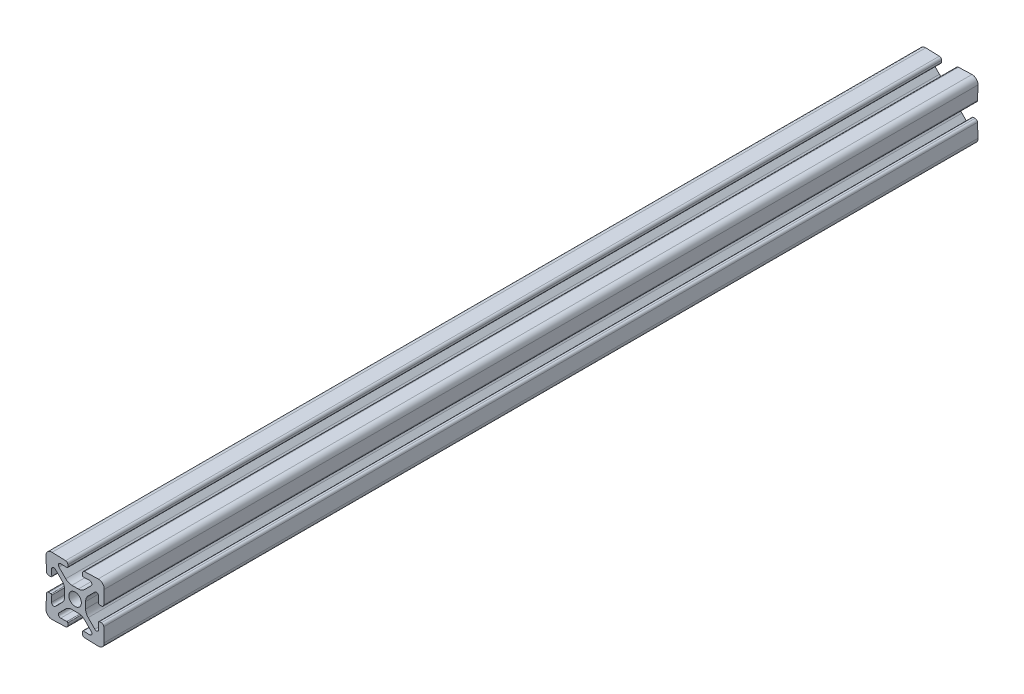
SolidWorks part; units mm, degrees
ref_plane "Front Plane" through (0, 0, 0) normal (0, 0, 1) x (1, 0, 0)
ref_plane "Top Plane" through (0, 0, 0) normal (0, 1, 0) x (1, 0, 0)
ref_plane "Right Plane" through (0, 0, 0) normal (1, 0, 0) x (0, 0, -1)
sketch "Sketch1" plane through (0, 0, 0) normal (0, 0, 1) x (1, 0, 0)
  line L0 (0, 0) -> (0, 10) construction
  line L1 (0, 0) -> (10, 0) construction
  line L2 (0, 0) -> (-10, 10) construction
  line L3 (-7.9302, 9.9988) -> (-3.2721, 9.8361)
  line L4 (-10, 10) -> (0, 10) construction
  line L6 (-2.8352, 8.0198) -> (-4.953, 8.0937)
  line L10 (0, 3.6) -> (-1.1022, 3.6)
  line L11 (-3.2236, 4.4787) -> (-5.5244, 6.7796)
  line L24 (0, 0) -> (-10, 0) construction
  line L25 (-10, 0) -> (0, 0) construction
  line L26 (0, 0) -> (0, -10) construction
  line L27 (-10, -10) -> (-10, 10) construction
  line L28 (0, 10) -> (10, 10) construction
  line L29 (-2.5249, 8.3091) -> (-2.5005, 9.0087)
  line L30 (-10, -10) -> (10, -10) construction
  arc A0 (-9.4142, 9.4142) -> (-7.9302, 9.9988) centre (-8, 8) cw
  arc A5 (-3.2721, 9.8361) -> (-2.5005, 9.0087) centre (-3.3, 9.0366) cw
  arc A6 (-1.1022, 3.6) -> (-3.2236, 4.4787) centre (-1.1022, 6.6) cw
  circle A16 centre (0, 0) radius 2.15
  arc A18 (-5.5244, 6.7796) -> (-4.953, 8.0937) centre (-4.9799, 7.3241) cw
  arc A20 (-2.8352, 8.0198) -> (-2.5249, 8.3091) centre (-2.8247, 8.3196) ccw
  point P15 (0, 0)
  point P42 (-2.3449, 3.6)
  point P80 (-10, 0)
  point P85 (0, -10)
  point P88 (0, -10)
  dimension "D11" = 2
  dimension "D15" = 3
  dimension "D4" = 0.7701
  dimension "D3" = 1.775
  dimension "Center Hole Diameter" = 4.3
  dimension "D5" = 11.5
  dimension "D6" = 9.9598
  dimension "D7" = 0.8
  dimension "D8" = 0.3
  dimension "D1" = 45
  dimension "D2" = 2
  dimension "Rail Width" = 20
  dimension "T-Slot Width" = 5
  dimension "D9" = 1.8
  dimension "D23" = 7.2
  dimension "T-Slot Depth" = 6.4
  dimension "Rail Height" = 20
sketch "Sketch3" plane through (0, 0, 0) normal (0, 0, 1) x (1, 0, 0)
  line L0 (-2.5249, 8.3091) -> (-2.5005, 9.0087) construction
  line L1 (0, 0) -> (-10, 10) construction
  line L2 (0, 0) -> (-10, 10) construction
  line L5 (-7.9302, 9.9988) -> (-3.2721, 9.8361) construction
  line L6 (-2.8352, 8.0198) -> (-4.953, 8.0937) construction
  line L17 (-2.5249, 8.3091) -> (-2.5005, 9.0087)
  line L19 (-2.8352, 8.0198) -> (-4.953, 8.0937)
  line L20 (0, 0) -> (0, 10) construction
  line L21 (-3.6, 0) -> (-2.15, 0)
  line L22 (-3.6, 0) -> (-3.6, 1.1022)
  line L23 (-4.4787, 3.2236) -> (-6.7796, 5.5244)
  line L42 (-3.2236, 4.4787) -> (-5.5244, 6.7796) construction
  line L43 (0, 3.6) -> (-1.1022, 3.6) construction
  line L44 (-7.9302, 9.9988) -> (-3.2721, 9.8361)
  line L47 (-3.2236, 4.4787) -> (-5.5244, 6.7796)
  line L48 (0, 3.6) -> (-1.1022, 3.6)
  line L59 (0, 3.6) -> (0, 2.15)
  line L60 (-9.9988, 7.9302) -> (-9.8361, 3.2721)
  line L61 (-8.0198, 2.8352) -> (-8.0937, 4.953)
  line L62 (-8.3091, 2.5249) -> (-9.0087, 2.5005)
  arc A0 (-7.9302, 9.9988) -> (-9.4142, 9.4142) centre (-8, 8) ccw construction
  arc A1 (-2.8352, 8.0198) -> (-2.5249, 8.3091) centre (-2.8247, 8.3196) ccw construction
  arc A3 (-2.8352, 8.0198) -> (-2.5249, 8.3091) centre (-2.8247, 8.3196) ccw
  arc A5 (-7.9302, 9.9988) -> (-9.9988, 7.9302) centre (-8, 8) ccw
  circle A13 centre (0, 0) radius 2.15 construction
  arc A14 (0, 2.15) -> (-2.15, 0) centre (0, 0) ccw
  arc A15 (-4.4787, 3.2236) -> (-3.6, 1.1022) centre (-6.6, 1.1022) cw
  arc A16 (-8.0937, 4.953) -> (-6.7796, 5.5244) centre (-7.3241, 4.9799) cw
  arc A17 (-9.0087, 2.5005) -> (-9.8361, 3.2721) centre (-9.0366, 3.3) cw
  arc A18 (-8.0198, 2.8352) -> (-8.3091, 2.5249) centre (-8.3196, 2.8247) cw
  arc A36 (-2.5005, 9.0087) -> (-3.2721, 9.8361) centre (-3.3, 9.0366) ccw construction
  arc A38 (-4.953, 8.0937) -> (-5.5244, 6.7796) centre (-4.9799, 7.3241) ccw construction
  arc A39 (-3.2236, 4.4787) -> (-1.1022, 3.6) centre (-1.1022, 6.6) ccw construction
  arc A41 (-2.5005, 9.0087) -> (-3.2721, 9.8361) centre (-3.3, 9.0366) ccw
  arc A43 (-4.953, 8.0937) -> (-5.5244, 6.7796) centre (-4.9799, 7.3241) ccw
  arc A44 (-3.2236, 4.4787) -> (-1.1022, 3.6) centre (-1.1022, 6.6) ccw
extrude "Boss-Extrude1" add sketch "Sketch3" along normal mid plane 300
pattern_circular "CirPattern1" count 4 over 360 about axis through (0, 0, 150) along (0, 0, -1) of bodies 104
combine bodies "Combine1" operation type add bodies to combine 111 112 113 104
equation "\"D1@Boss-Extrude1\"=\"lenght\""
equation "\"lenght\"= 300"
